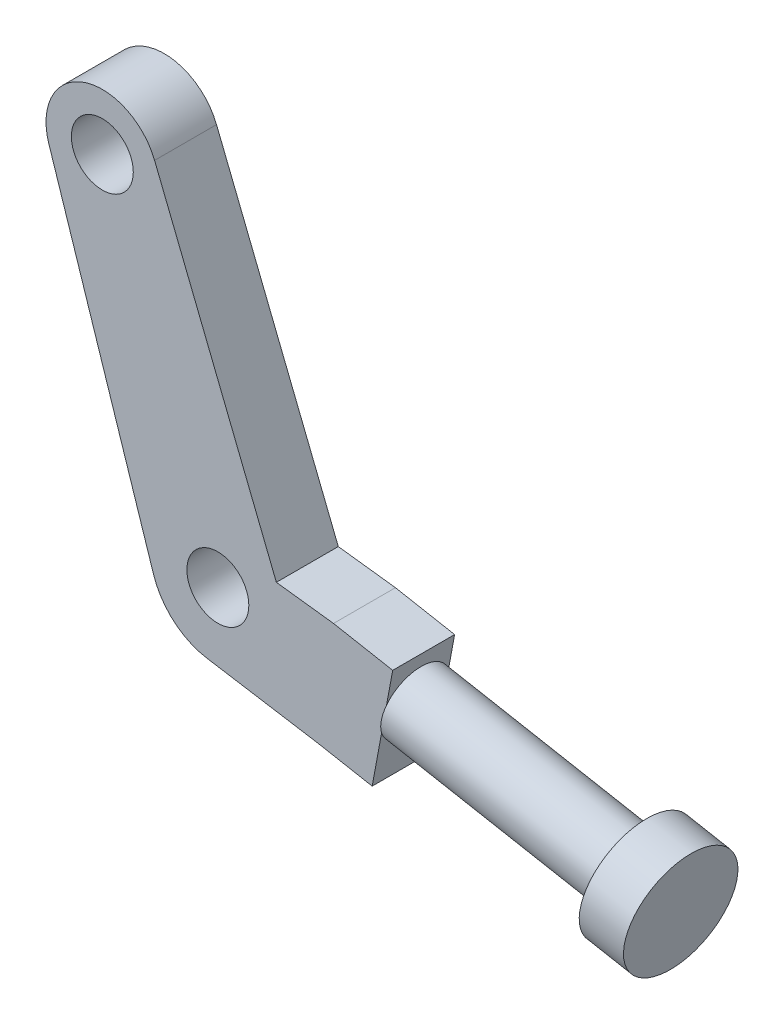
SolidWorks part; units mm, degrees
ref_plane "Front Plane" through (0, 0, 0) normal (0, 0, 1) x (1, 0, 0)
ref_plane "Top Plane" through (0, 0, 0) normal (0, 1, 0) x (1, 0, 0)
ref_plane "Right Plane" through (0, 0, 0) normal (1, 0, 0) x (0, 0, -1)
sketch "Sketch1" plane through (0, 0, 0) normal (0, 0, 1) x (1, 0, 0)
  line L0 (0, 0) -> (12.2673, -3.287) construction
  line L1 (0, 0) -> (-13.031, 35.8023) construction
  line L2 (0, 0) -> (124.5155, 0) construction
  line L7 (13.0444, 3.0153) -> (19.7217, 1.7757)
  line L8 (-7.2434, -2.3661) -> (-19.0671, 33.8306)
  line L9 (-1.2263, -7.5207) -> (11.2454, -9.5542)
  line L10 (-7.1348, 38.1597) -> (6.5991, 3.81)
  line L11 (6.5991, 3.81) -> (13.0444, 3.0153)
  line L12 (0, 0) -> (6.5991, 3.81) construction
  line L13 (19.7217, 1.7757) -> (17.4062, -10.6979)
  line L14 (17.4062, -10.6979) -> (11.2454, -9.5542)
  circle A2 centre (-13.031, 35.8023) radius 3.4925
  circle A9 centre (-13.031, 35.8023) radius 6.35 construction
  circle A10 centre (12.2673, -3.287) radius 6.35 construction
  circle A11 centre (0, 0) radius 7.62 construction
  arc A12 (-19.0671, 33.8306) -> (-7.1348, 38.1597) centre (-13.031, 35.8023) cw
  arc A14 (-7.2434, -2.3661) -> (-1.2263, -7.5207) centre (0, 0) ccw
  circle A15 centre (0, 0) radius 3.4925
  point P4 (50.7, -19.8721)
  point P10 (41.4526, -17.5255)
  dimension "D5" = 6.985
  dimension "D7" = 6.985
  dimension "D12" = 12.7
  dimension "D13" = 15.24
  dimension "D14" = 12.7
  dimension "D1" = 15
  dimension "D2" = 110
  dimension "D3" = 12.7
  dimension "D4" = 38.1
  dimension "D15" = 30
extrude "Boss-Extrude1" add sketch "Sketch1" along normal mid plane 6.985
sketch "Sketch2" plane through (18.7461, -3.4799, 0) normal (0.9832, -0.1825, 0) x (0, 0, -1)
  circle A0 centre (0, 0) radius 3.81
  dimension "D1" = 7.62
extrude "Boss-Extrude2" add sketch "Sketch2" along normal blind 25.4
sketch "Sketch3" plane through (43.7194, -8.1159, 0) normal (0.9832, -0.1825, 0) x (0, 0, -1)
  circle A0 centre (0, 0) radius 6.35
  dimension "D1" = 12.7
extrude "Boss-Extrude3" add sketch "Sketch3" along normal blind 5.08
